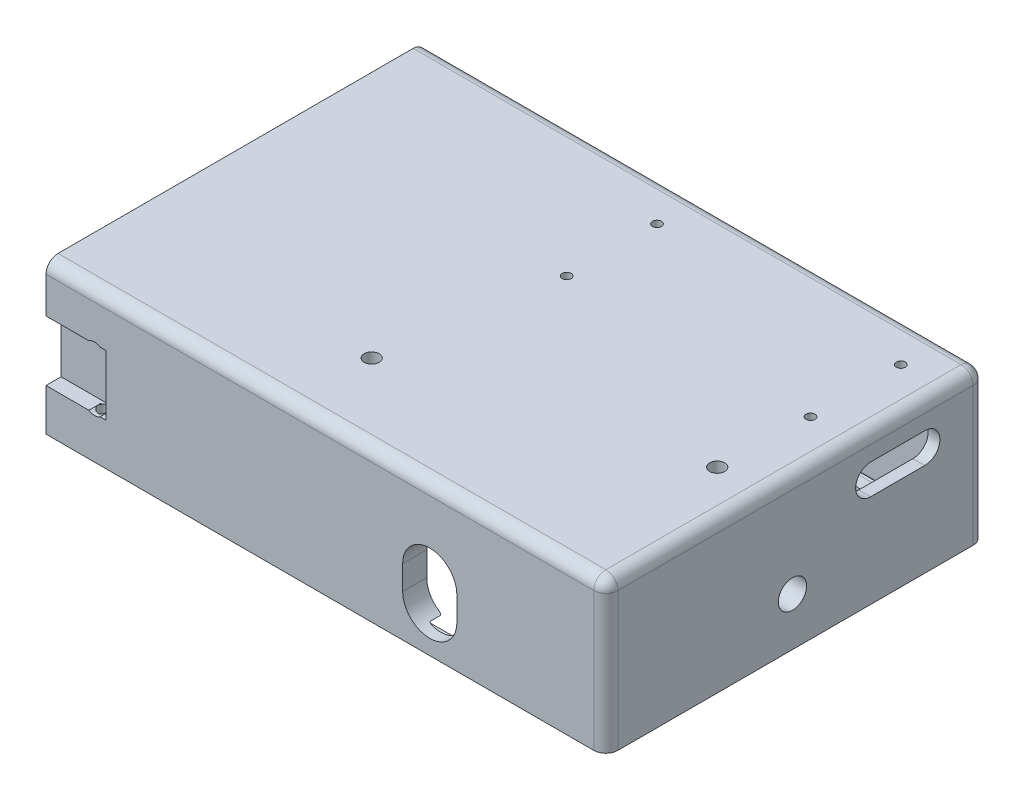
SolidWorks part; units mm, degrees
ref_plane "Front Plane" through (0, 0, 0) normal (0, 0, 1) x (1, 0, 0)
ref_plane "Top Plane" through (0, 0, 0) normal (0, 1, 0) x (1, 0, 0)
ref_plane "Right Plane" through (0, 0, 0) normal (1, 0, 0) x (0, 0, -1)
sketch "Sketch1" plane through (0, 0, 0) normal (0, 1, 0) x (1, 0, 0)
  line L1 (0, 0) -> (95, 0)
  line L2 (0, 0) -> (0, 63)
  line L3 (0, 63) -> (95, 63)
  line L4 (95, 0) -> (95, 63)
  line L5 (2, 4) -> (93, 4)
  line L6 (2, 4) -> (2, 59)
  line L7 (2, 59) -> (93, 59)
  line L8 (93, 4) -> (93, 59)
  line L9 (0, 0) -> (2, 0)
  line L10 (0, 0) -> (0, 63)
  line L11 (0, 63) -> (2, 63)
  line L12 (2, 0) -> (2, 63)
  dimension "D1" = 63
  dimension "Length" = 95
  dimension "D2" = 2
  dimension "D3" = 4
  dimension "D4" = 2
  dimension "D5" = 4
extrude "Boss-Extrude2" add sketch "Sketch1" along normal blind 25 contours L1 L4 L3 L2
extrude "Cut-Extrude1" cut sketch "Sketch1<4>" along normal blind 23 contours L5 L8 L7 L6
sketch "Sketch1<4>" plane through (0, 0, 0) normal (0, 1, 0) x (1, 0, 0) same geometry as "Sketch1"
sketch "Sketch4" plane through (0, 23, 0) normal (0, -1, 0) x (1, 0, 0)
  line L0 (2, -4) -> (93, -4) construction
  line L1 (29.5, -4) -> (31.5, -4)
  line L2 (29.5, -4) -> (29.5, -59)
  line L3 (29.5, -59) -> (31.5, -59)
  line L4 (31.5, -4) -> (31.5, -59)
  line L5 (2, -59) -> (93, -59) construction
  line L6 (2, -4) -> (2, -59) construction
  dimension "D1" = 2
  dimension "D2" = 27.5
extrude "Boss-Extrude3" add sketch "Sketch4" along normal blind 19
fillet "Fillet1" radius 2 8 edges at (47.5, 25, -63) (0, 12.5, -63) (0, 25, -31.5) (0, 12.5, 0) (47.5, 25, 0) (95, 12.5, 0) (95, 25, -31.5) (95, 12.5, -63)
sketch "Sketch5" plane through (0, 0, 0) normal (0, -1, 0) x (-1, 0, 0)
  line L1 (0, 0) -> (-2, 0)
  line L2 (0, 0) -> (0, 63)
  line L3 (0, 63) -> (-2, 63)
  line L4 (-2, 0) -> (-2, 63)
extrude "Cut-Extrude3" cut sketch "Sketch5" against normal through all
sketch "Sketch6" plane through (2, 0, 0) normal (-1, 0, 0) x (0, 0, 1)
  line L0 (-4, 23) -> (-4, 0) construction
  line L1 (-4, 0.75) -> (-1.8, 0.75)
  line L2 (-4, 0.75) -> (-4, 2.95)
  line L3 (-4, 2.95) -> (-1.8, 2.95)
  line L4 (-1.8, 0.75) -> (-1.8, 2.95)
  line L5 (-59, 23) -> (-59, 0) construction
  line L6 (-59, 0.75) -> (-61.2, 0.75)
  line L7 (-59, 0.75) -> (-59, 2.95)
  line L8 (-59, 2.95) -> (-61.2, 2.95)
  line L9 (-61.2, 0.75) -> (-61.2, 2.95)
  line L10 (0, 0) -> (-63, 0) construction
  line L11 (0, 23) -> (0, 0) construction
  point P12 (-60.1, 2.95)
  point P17 (-1.8, 1.85)
  dimension "D1" = 2.2
  dimension "D2" = 2.2
  dimension "D3" = 2.2
  dimension "D4" = 0.75
  dimension "D5" = 0.75
  dimension "1.5" = 2.2
  dimension "D6" = 1.8
extrude "Cut-Extrude4" cut sketch "Sketch6" against normal blind 85 contours L6 L9 L8 L7 | L1 L4 L3 L2
sketch "Sketch7" plane through (0, 0, -63) normal (0, 0, -1) x (-1, 0, 0)
  line L0 (-2, 0) -> (-2, 23) construction
  line L1 (-2, 7) -> (-12, 7)
  line L2 (-2, 7) -> (-2, 17)
  line L3 (-2, 17) -> (-12, 17)
  line L4 (-12, 7) -> (-12, 17)
  line L5 (-93, 25) -> (-2, 25) construction
  dimension "D1" = 10
  dimension "D2" = 8
  dimension "D3" = 10
extrude "Cut-Extrude5" cut sketch "Sketch7" against normal blind 2.5
sketch "Sketch8" plane through (0, 7, 0) normal (0, 1, 0) x (1, 0, 0)
  line L0 (12, 60.5) -> (12, 63) construction
  line L1 (12, 60.5) -> (2, 60.5) construction
  circle A0 centre (10, 61.5) radius 0.875
  dimension "D1" = 1.75
  dimension "D2" = 2
  dimension "D3" = 1
extrude "Cut-Extrude6" cut sketch "Sketch8" against normal blind 1.5 and the other way blind 11.5
sketch "Sketch9" plane through (0, 0, 0) normal (0, 0, 1) x (1, 0, 0)
  line L0 (2, 23) -> (2, 0) construction
  line L1 (2, 7) -> (12, 7)
  line L2 (2, 7) -> (2, 17)
  line L3 (2, 17) -> (12, 17)
  line L4 (12, 7) -> (12, 17)
  line L5 (2, 25) -> (93, 25) construction
  dimension "D1" = 10
  dimension "D2" = 10
  dimension "D3" = 8
extrude "Cut-Extrude7" cut sketch "Sketch9" against normal blind 2.5
sketch "Sketch10" plane through (0, 7, 0) normal (0, 1, 0) x (1, 0, 0)
  line L0 (12, 2.5) -> (12, 0) construction
  line L1 (2, 2.5) -> (12, 2.5) construction
  circle A0 centre (10, 1.5) radius 0.875
  dimension "D1" = 1.75
  dimension "D2" = 2
  dimension "D3" = 1
extrude "Cut-Extrude8" cut sketch "Sketch10" against normal blind 1.5 and the other way blind 11.5
sketch "Sketch11" plane through (0, 0, -63) normal (0, 0, -1) x (-1, 0, 0)
  line L0 (-12, 7) -> (-2, 7) construction
  line L1 (-9.123, 7) -> (-10.8, 7)
  line L2 (-12, 12) -> (-17.0656, 12) construction
  line L3 (-12, 17) -> (-12, 7) construction
  line L4 (-9.123, 17) -> (-10.8, 17)
  spline S0 degree 2 poles (-10.8, 7) (-9.9802, 6.3956) (-9.123, 7) knots 0 0 0 1 1 1
  spline S1 degree 2 poles (-10.8, 17) (-9.9802, 17.6044) (-9.123, 17) knots 0 0 0 1 1 1
  dimension "D1" = 0.3
  dimension "D2" = 1.2
extrude "Cut-Extrude9" cut sketch "Sketch11" against normal blind 2 contours S0 L1 | S1 L4
sketch "Sketch12" plane through (0, 0, 0) normal (0, 0, 1) x (1, 0, 0)
  line L0 (2, 7) -> (12, 7) construction
  line L2 (11, 7) -> (9.1201, 7)
  line L3 (12, 12) -> (18.6065, 12) construction
  line L4 (12, 7) -> (12, 17) construction
  line L5 (11, 17) -> (9.1201, 17)
  spline S0 degree 2 poles (11, 7) (10.0566, 6.3998) (9.1201, 7) knots 0 0 0 1 1 1
  spline S1 degree 2 poles (11, 17) (10.0566, 17.6002) (9.1201, 17) knots 0 0 0 1 1 1
  dimension "D1" = 0.3
  dimension "D2" = 1
extrude "Cut-Extrude10" cut sketch "Sketch12" against normal blind 2 contours S0 L2 | S1 L5
sketch "Sketch13" plane through (0, 23, 0) normal (0, -1, 0) x (-1, 0, 0)
  line L0 (-93, 4) -> (-93, 59) construction
  line L1 (-2, 4) -> (-93, 4) construction
  line L2 (-93, 2) -> (-93, 61) construction
  line L4 (-93, 61) -> (-2, 61) construction
  circle A0 centre (-47.5, 56) radius 0.75
  circle A1 centre (-47.5, 41) radius 0.75
  circle A2 centre (-88, 41) radius 0.75
  circle A3 centre (-88, 56) radius 0.75
  dimension "D1" = 1.5
  dimension "D2" = 1.5
  dimension "D3" = 1.5
  dimension "D4" = 1.5
  dimension "D5" = 15
  dimension "D6" = 15
  dimension "D7" = 40.5
  dimension "D8" = 5
  dimension "D9" = 37
  dimension "D10" = 5
  dimension "D11" = 40.5
  dimension "D12" = 5
extrude "Cut-Extrude11" cut sketch "Sketch13" against normal through all
fillet "Fillet2" radius 0.3 12 edges at (44.5, 2.95, -4) (44.5, 2.95, -1.8) (2, 1.85, -1.8) (2, 2.95, -2.9) (44.5, 2.95, -59) (44.5, 0.75, -61.2) (44.5, 2.95, -61.2) (2, 2.95, -60.1) (2, 0.75, -60.1) (2, 1.85, -61.2) (2, 0.75, -2.9) (44.5, 0.75, -1.8)
sketch "Sketch15" plane through (29.5, 0, 0) normal (-1, 0, 0) x (0, 0, 1)
  line L0 (-4, 23) -> (-59, 23) construction
  line L1 (-4, 4) -> (-9, 4)
  line L2 (-4, 4) -> (-4, 23)
  line L3 (-4, 23) -> (-9, 23)
  line L4 (-9, 4) -> (-9, 23)
  dimension "D1" = 5
extrude "Cut-Extrude13" cut sketch "Sketch15" against normal up to next
fillet "Fillet3" radius 0.5 6 edges at (31.5, 13.5, -59) (29.5, 13.5, -59) (31.5, 4, -34) (29.5, 4, -34) (30.5, 4, -9) (30.5, 4, -59)
sketch "Sketch16" plane through (0, 23, 0) normal (0, -1, 0) x (1, 0, 0)
  line L0 (2, -4) -> (93, -4) construction
  line L1 (93, -4) -> (93, -59) construction
  line L2 (31.5, -58.5) -> (31.5, -9) construction
  circle A0 centre (87.5, -26) radius 1.25
  circle A1 centre (43.1, -13) radius 1.25
  dimension "D3" = 2.5
  dimension "D4" = 2.5
  dimension "D1" = 44.4
  dimension "D2" = 13
  dimension "D5" = 9
  dimension "D6" = 5.5
  dimension "D7" = 11.6
sketch "Sketch17" plane through (0, 0, 0) normal (0, 0, 1) x (1, 0, 0)
  line L0 (65.75, 11) -> (65.75, 7) construction
  line L1 (70.25, 11) -> (70.25, 7)
  line L2 (61.25, 11) -> (61.25, 7)
  line L4 (93, 0) -> (93, 23) construction
  line L5 (93, 23) -> (2, 23) construction
  arc A0 (70.25, 11) -> (61.25, 11) centre (65.75, 11) ccw
  arc A1 (61.25, 7) -> (70.25, 7) centre (65.75, 7) ccw
  point P2 (65.75, 9)
  dimension "D1" = 9
  dimension "D2" = 27.25
  dimension "D3" = 4
  dimension "D4" = 12
extrude "Cut-Extrude14" cut sketch "Sketch17" against normal up to next contours L2 A1 L1 A0
extrude "Cut-Extrude15" cut sketch "Sketch16" against normal up to next contours A0 | A1
sketch "Sketch18" plane through (95, 0, 0) normal (1, 0, 0) x (0, 0, -1)
  line L0 (53, 18) -> (44, 18) construction
  line L1 (53, 15.5) -> (44, 15.5)
  line L2 (53, 20.5) -> (44, 20.5)
  line L3 (61, 0) -> (61, 23) construction
  line L4 (61, 23) -> (2, 23) construction
  line L5 (4, 0) -> (59, 0) construction
  arc A0 (53, 15.5) -> (53, 20.5) centre (53, 18) ccw
  arc A1 (44, 20.5) -> (44, 15.5) centre (44, 18) ccw
  circle A2 centre (31, 8) radius 2.35
  point P2 (48.5, 18)
  dimension "D5" = 4.7
  dimension "D1" = 5
  dimension "D2" = 9
  dimension "D3" = 8
  dimension "D4" = 5
  dimension "D6" = 8
  dimension "D7" = 30
extrude "Cut-Extrude16" cut sketch "Sketch18" against normal blind 8 draft 1 contours L2 A1 L1 A0 region at (95, 18, -48.5) draft outward yes
sketch "Sketch19" plane through (93, 0, 0) normal (-1, 0, 0) x (0, 0, 1)
  circle A0 centre (-31, 8) radius 3.75
  circle A1 centre (-31, 8) radius 2.35 construction
  dimension "D1" = 7.5
extrude "Boss-Extrude4" add sketch "Sketch19" along normal blind 5 contours A0
extrude "Cut-Extrude17" cut sketch "Sketch18<3>" against normal blind 10 draft 2 contours A2 draft outward yes
sketch "Sketch18<3>" plane through (95, 0, 0) normal (1, 0, 0) x (0, 0, -1) same geometry as "Sketch18"
sketch "Sketch20" plane through (31.5, 0, 0) normal (1, 0, 0) x (0, 0, -1)
  line L0 (59, 23) -> (59, 4.5) construction
  line L1 (58.5, 23) -> (9, 23) construction
  circle A0 centre (56, 21) radius 0.75
  circle A1 centre (15.5, 21) radius 0.75
  circle A2 centre (15.5, 6) radius 0.75
  circle A3 centre (56, 6) radius 0.75
  dimension "D1" = 1.5
  dimension "D2" = 1.5
  dimension "D3" = 1.5
  dimension "D4" = 1.5
  dimension "D5" = 15
  dimension "D6" = 15
  dimension "D7" = 40.5
  dimension "D8" = 3
  dimension "D9" = 40.5
  dimension "D10" = 2
extrude "Cut-Extrude18" cut sketch "Sketch20" against normal blind 10 contours A2 | A1 | A3 | A0
sketch "Sketch21" plane through (0, 0, -63) normal (0, 0, -1) x (-1, 0, 0)
  line L0 (-35, 10.5) -> (-35, 17.5) construction
  line L1 (-38, 10.5) -> (-38, 17.5)
  line L2 (-32, 10.5) -> (-32, 17.5)
  line L3 (-2, 23) -> (-93, 23) construction
  line L4 (-2, 0) -> (-2, 7) construction
  arc A0 (-38, 10.5) -> (-32, 10.5) centre (-35, 10.5) ccw
  arc A1 (-32, 17.5) -> (-38, 17.5) centre (-35, 17.5) ccw
  point P2 (-35, 14)
  dimension "D1" = 9
  dimension "D2" = 7
  dimension "D3" = 6
  dimension "D4" = 30
extrude "Cut-Extrude19" cut sketch "Sketch21" against normal blind 10
equation "\"D10@Sketch13\"=\"D8@Sketch13\""
equation "\"D11@Sketch13\"=\"D7@Sketch13\""
equation "\"D3@Sketch13\"=\"D4@Sketch13\""
equation "\"D2@Sketch13\"=\"D4@Sketch13\""
equation "\"D1@Sketch13\"=\"D4@Sketch13\""
equation "\"D3@Sketch20\"=\"D2@Sketch20\""
equation "\"D4@Sketch20\"=\"D2@Sketch20\""
equation "\"D1@Sketch20\"=\"D2@Sketch20\""
equation "\"D9@Sketch20\"=\"D7@Sketch20\""
equation "\"D6@Sketch20\"=\"D5@Sketch20\""
